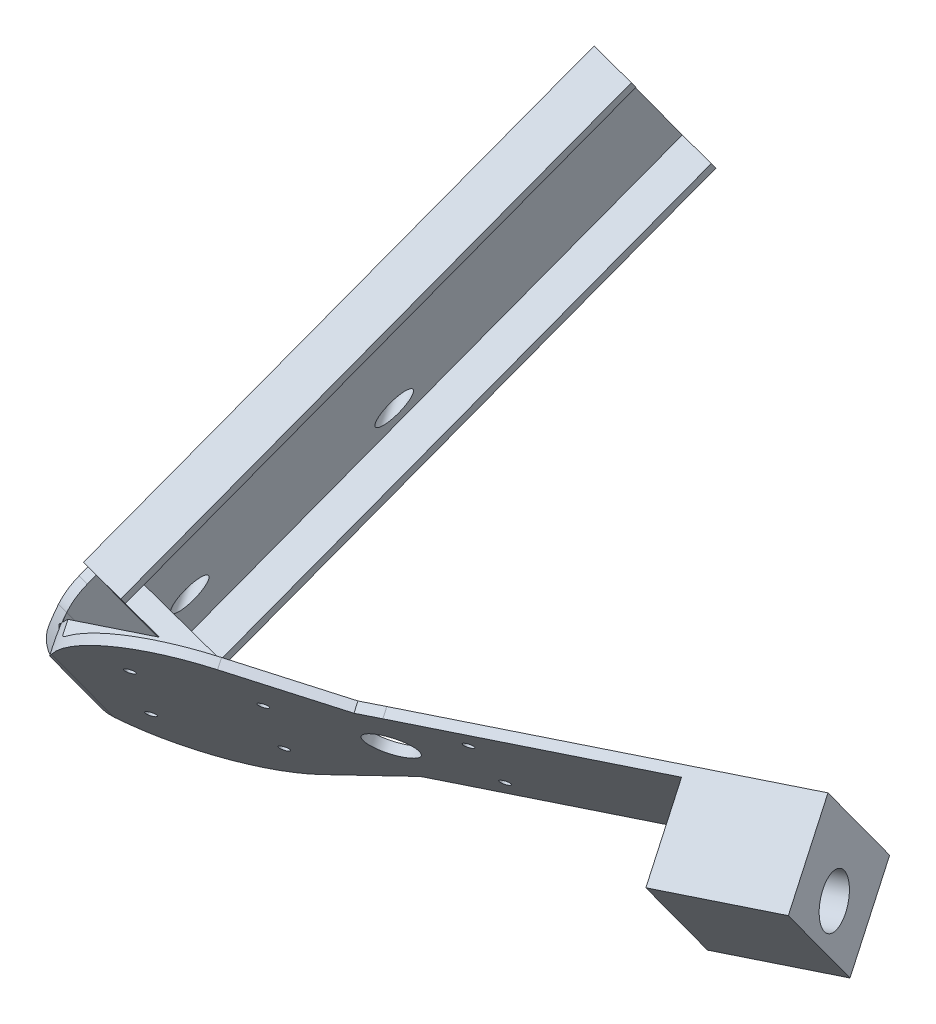
SolidWorks part; units mm, degrees
ref_plane "Front Plane" through (0, 0, 0) normal (0, 0, 1) x (1, 0, 0)
ref_plane "Top Plane" through (0, 0, 0) normal (0, 1, 0) x (1, 0, 0)
ref_plane "Right Plane" through (0, 0, 0) normal (1, 0, 0) x (0, 0, -1)
sketch "Sketch2" plane through (20.5367, -40.368, 48.4426) normal (-0.3097, 0.6087, -0.7305) x (-0.9432, -0.0997, 0.3168)
  line L14 (99.8599, 39.0261) -> (80.3467, 30.0123)
  line L15 (80.3467, 30.0123) -> (75.4661, 30.0566)
  line L16 (75.4661, 30.0566) -> (53.4661, 30.0566)
  line L17 (53.4661, 30.0566) -> (53.4661, 3.0572)
  line L18 (53.4661, 3.0572) -> (75.3438, 3.0572)
  line L19 (75.3438, 3.0572) -> (79.5451, 3.0191)
  line L20 (79.5451, 3.0191) -> (99.8599, -6.365)
  arc A2 (99.8599, -6.365) -> (99.8599, 39.0261) centre (110.3438, 16.3306) ccw
  circle A7 centre (118.4981, 28.9205) radius 1
  circle A8 centre (122.9337, 8.1762) radius 1
  circle A9 centre (102.1894, 3.7406) radius 1
  circle A10 centre (97.7538, 24.4849) radius 1
extrude "Boss-Extrude1" add sketch "Sketch2" along normal blind 2
ref_plane "Plane2" through (-127.6606, -13.4871, 42.8812) normal (-0.9432, -0.0997, 0.3168) x (0.3173, 0.0115, 0.9483)
sketch "Sketch5" plane through (19.9173, -39.1506, 46.9817) normal (-0.3097, 0.6087, -0.7305) x (-0.9432, -0.0997, 0.3168)
  line L0 (135.3438, 30.0566) -> (135.3438, 0)
  line L1 (135.3438, -27.1851) -> (135.3438, 27.1851) construction
  line L2 (135.3438, 30.0566) -> (53.4661, 30.0566) construction
  line L3 (53.4661, 30.0566) -> (53.4661, 3.0572) construction
  line L4 (75.4661, 30.0566) -> (53.4661, 30.0566) construction
  line L5 (53.4661, 30.0566) -> (53.4661, 3.0572) construction
  line L6 (53.4661, 3.0572) -> (135.3438, 3.0572) construction
ref_plane "Plane3" through (-82.6453, 18.546, -7.7268) normal (-0.9717, 0.2181, -0.0908) x (-0.1201, -0.7871, -0.605)
sketch "Sketch7" plane through (-82.6453, 18.546, -7.7268) normal (-0.9717, 0.2181, -0.0908) x (-0.1201, -0.7871, -0.605)
  line L0 (-32.8306, 125.1046) -> (-16.3306, 131.4663) construction
  line L5 (-41.3306, 110.8725) -> (8.6694, 110.8725) construction
  line L6 (-16.3306, 110.8725) -> (-16.3306, 131.4663) construction
  line L7 (-32.8306, 125.1046) -> (0.1694, 125.1046)
  line L8 (-32.8306, 125.1046) -> (-32.8306, 0.9406)
  line L9 (-32.8306, 0.9406) -> (0.1694, 0.9406)
  line L10 (0.1694, 125.1046) -> (0.1694, 0.9406)
  line L11 (-16.3306, 131.4663) -> (0.1694, 125.1046) construction
  ellipse E0 centre (-16.3306, 112.6046) end of major axis (-41.3306, 112.6046) minor radius 12.5 (6.365, 107.3626) -> (-39.0261, 107.3626) ccw construction
  dimension "D1" = 33
  dimension "D2" = 124.164
extrude "Boss-Extrude4" add sketch "Sketch7" against normal blind 2
sketch "Sketch8" plane through (20.5367, -40.368, 48.4426) normal (0.3097, -0.6087, 0.7305) x (0.9508, 0.1982, -0.2379)
  circle A0 centre (-76.6465, 26.2189) radius 4.75
  dimension "D1" = 9.5
extrude "Cut-Extrude1" cut sketch "Sketch8" against normal up to next
sketch "Sketch10" plane through (20.5367, -40.368, 48.4426) normal (0.3097, -0.6087, 0.7305) x (0.9508, 0.1982, -0.2379)
  circle A0 centre (-123.8351, 33.3692) radius 33.6087
extrude "Cut-Extrude2" cut sketch "Sketch10" along normal blind 2
fillet "Fillet5" radius 3 1 edges at (-103.6043, -39.5536, 99.0114)
sketch "Sketch11" plane through (-80.7019, 18.1099, -7.5451) normal (0.9717, -0.2181, 0.0908) x (0.0886, -0.0199, -0.9959)
  line L4 (-118.8575, -49.576) -> (-20.6925, 25.5059) construction
  line L5 (-108.7694, -41.86) -> (-118.8575, -49.576)
  line L6 (-0.6442, -0.706) -> (-98.8092, -75.7879) construction
  line L7 (-90.6097, -69.5165) -> (-98.5614, -75.5983)
  line L8 (-113.3959, -56.7166) -> (-122.236, -62.9515)
  line L9 (-122.236, -62.9515) -> (-127.4435, -56.143)
  line L10 (-127.4435, -56.143) -> (-118.8575, -49.576)
  line L11 (-98.5614, -75.5983) -> (-107.3952, -82.3549)
  line L12 (-107.3952, -82.3549) -> (-112.8567, -75.2142)
  line L13 (-112.8567, -75.2142) -> (-104.2708, -68.6472)
  arc A0 (-111.9091, -46.3062) -> (-108.7694, -41.86) centre (-102.9159, -49.3252) cw
  arc A1 (-93.8342, -69.938) -> (-90.6097, -69.5165) centre (-95.1843, -47.0658) ccw
  ellipse E0 centre (-70.9526, -33.7087) end of major axis (-110.6677, -64.0849) minor radius 25 (-104.2708, -68.6472) -> (-93.8342, -69.938) ccw construction
  ellipse E1 centre (-70.9526, -33.7087) end of major axis (-110.6677, -64.0849) minor radius 25 (-111.9091, -46.3062) -> (-113.3959, -56.7166) ccw construction
  ellipse E2 centre (-70.9526, -33.7087) end of major axis (-110.6677, -64.0849) minor radius 25 (-104.2708, -68.6472) -> (-93.8342, -69.938) ccw
  ellipse E3 centre (-70.9526, -33.7087) end of major axis (-110.6677, -64.0849) minor radius 25 (-111.9091, -46.3062) -> (-113.3959, -56.7166) ccw
extrude "Cut-Extrude3" cut sketch "Sketch11" against normal blind 2
fillet "Fillet6" radius 3 1 edges at (-106.1336, -40.7743, 101.1199)
fillet "Fillet7" radius 3 1 edges at (-105.1619, -40.9923, 101.2107)
sketch "Sketch12" plane through (19.9173, -39.1506, 46.9817) normal (-0.3097, 0.6087, -0.7305) x (-0.9508, -0.1982, 0.2379)
  line L0 (122.6698, 48.7105) -> (108.6205, 46.9221)
  line L1 (124.388, 48.9292) -> (69.3888, 41.9282) construction
  line L2 (108.6205, 46.9221) -> (112.7875, 14.1862)
  line L3 (73.5558, 9.1923) -> (129.7344, 16.3434) construction
  line L4 (112.7875, 14.1862) -> (126.8363, 15.9745)
  line L5 (127.0079, 14.6264) -> (122.4977, 50.0585) construction
  line L7 (108.6205, 46.9221) -> (122.6698, 48.7105)
  line L8 (122.6698, 48.7105) -> (126.5456, 49.2038)
  line L9 (126.5456, 49.2038) -> (130.7126, 16.468)
  line L10 (130.7126, 16.468) -> (126.8363, 15.9745)
  circle A0 centre (120.9172, 23.6341) radius 1 construction
  circle A1 centre (113.8977, 43.6522) radius 1 construction
  circle A2 centre (120.9172, 23.6341) radius 1
  circle A3 centre (113.8977, 43.6522) radius 1
  circle M10 centre (113.8977, 43.6522) radius 1
  circle M11 centre (120.9172, 23.6341) radius 1
  line M14 (127.0079, 14.6264) -> (122.4977, 50.0585)
extrude "Boss-Extrude5" add sketch "Sketch12" along normal blind 3 contours L2 L4 L0 M14 M10 M11 | L10 L9 L8 L0 M14 region at (-100.5459, -39.2305, 97.9841) region at (-92.0281, -38.354, 95.1034)
sketch "Sketch13" plane through (18.9883, -37.3245, 44.7903) normal (-0.3097, 0.6087, -0.7305) x (-0.9508, -0.1982, 0.2379)
  circle A0 centre (113.8977, 43.6522) radius 2
  circle A1 centre (120.9172, 23.6341) radius 2
  dimension "D1" = 4
extrude "Cut-Extrude4" cut sketch "Sketch13" against normal blind 3
sketch "Sketch14" plane through (20.5367, -40.368, 48.4426) normal (0.3097, -0.6087, 0.7305) x (0.9508, 0.1982, -0.2379)
  line L0 (-126.5456, 49.2038) -> (-126.9975, 45.6535)
  line L1 (-126.5456, 49.2038) -> (-123.9462, 48.8729)
  line L2 (-130.2607, 20.0182) -> (-130.7126, 16.468)
  line L3 (-130.7126, 16.468) -> (-128.1132, 16.1371)
  arc A0 (-123.9462, 48.8729) -> (-126.9975, 45.6535) centre (-107.3984, 30.1334) ccw construction
  arc A1 (-123.9462, 48.8729) -> (-126.9975, 45.6535) centre (-107.3984, 30.1334) ccw
  arc A2 (-131.6151, 23.9243) -> (-129.9101, 19.2604) centre (-107.3984, 30.1334) ccw construction
  arc A3 (-130.2607, 20.0182) -> (-129.9101, 19.2604) centre (-107.3984, 30.1334) ccw
  arc A4 (-129.9101, 19.2604) -> (-99.8643, 6.2956) centre (-107.3984, 30.1334) ccw construction
  arc A5 (-129.9101, 19.2604) -> (-128.1132, 16.1371) centre (-107.3984, 30.1334) ccw
extrude "Cut-Extrude5" cut sketch "Sketch14" against normal up to surface (5 mm away) up to face at (-89.3106, -24.8328, 101.1118)
sketch "Sketch17" plane through (-80.7019, 18.1099, -7.5451) normal (0.9717, -0.2181, 0.0908) x (0.0886, -0.0199, -0.9959)
  line L0 (-107.2713, -40.7142) -> (-87.223, -66.9262) construction
  line L1 (-107.2713, -40.7142) -> (-87.223, -66.9262)
  line L2 (-107.2713, -40.7142) -> (-104.0941, -38.2841)
  line L3 (-108.7694, -41.86) -> (-20.6925, 25.5059) construction
  line L4 (-104.0941, -38.2841) -> (-84.0458, -64.4961)
  line L5 (-0.6442, -0.706) -> (-90.6097, -69.5165) construction
  line L6 (-84.0458, -64.4961) -> (-87.223, -66.9262)
  dimension "D1" = 4
extrude "Boss-Extrude7" add sketch "Sketch17" along normal up to vertex (15.2648 mm away) separate body up to point (-88.255, -48.7857, 80.704)
sketch "Sketch18" plane through (3.9419, 25.8413, 19.8629) normal (0.1201, 0.7871, 0.605) x (0.9928, -0.0952, -0.0732)
  line L0 (-88.058, -89.8018) -> (-75.4041, -92.451)
  line L1 (-74.815, -92.2576) -> (-56.2754, -86.1709) construction
  line L2 (-75.4041, -92.451) -> (-87.9418, -96.5673)
  line L3 (-87.9418, -96.5673) -> (-88.8776, -93.7169)
  line L4 (-88.8776, -93.7169) -> (-88.058, -89.8018)
  line L5 (-88.058, -89.8018) -> (-102.9988, -86.6738) construction
extrude "Boss-Extrude8" add sketch "Sketch18" against normal up to surface (33 mm away) up to face at (-95.2645, -45.9675, 78.4285)
sketch "Sketch16" plane through (19.9173, -39.1506, 46.9817) normal (-0.3097, 0.6087, -0.7305) x (-0.9508, -0.1982, 0.2379)
  circle A0 centre (120.9172, 23.6341) radius 2 construction
  circle A1 centre (113.8977, 43.6522) radius 2 construction
  circle A2 centre (120.9172, 23.6341) radius 2
  circle A3 centre (113.8977, 43.6522) radius 2
extrude "Cut-Extrude6" cut sketch "Sketch16" along normal through all
sketch "Sketch20" plane through (19.9173, -39.1506, 46.9817) normal (-0.3097, 0.6087, -0.7305) x (-0.9508, -0.1982, 0.2379)
  circle A0 centre (100.8991, 16.6145) radius 2
  dimension "D1" = 4
extrude "Cut-Extrude7" cut sketch "Sketch20" along normal through all
sketch "Sketch21" plane through (3.9419, 25.8413, 19.8629) normal (0.1201, 0.7871, 0.605) x (0.9928, -0.0952, -0.0732)
  line L0 (-83.4403, 16.5079) -> (-105.776, -90.1791)
  line L1 (-106.1625, -92.0251) -> (-83.4403, 16.5079) construction
  line L2 (-105.776, -90.1791) -> (-96.967, -92.0234)
  line L3 (-96.967, -92.0234) -> (-74.6312, 14.6636)
  line L4 (-74.6312, 14.6636) -> (-83.4403, 16.5079)
  line L5 (-88.8776, -93.7169) -> (-103.8185, -90.589) construction
  dimension "D1" = 9
extrude "Boss-Extrude9" add sketch "Sketch21" along normal blind 2
sketch "Sketch22" plane through (-0.0203, -0.1334, -0.1025) normal (-0.1201, -0.7871, -0.605) x (0.9928, -0.0952, -0.0732)
  line L3 (-105.776, 90.1791) -> (-96.967, 92.0234)
  line L11 (-88.8776, 93.7169) -> (-103.8185, 90.589) construction
  line L12 (-74.6312, -14.6636) -> (-96.967, 92.0234)
  line L13 (-96.1473, 88.1082) -> (-74.6312, -14.6636) construction
  line L14 (-105.776, 90.1791) -> (-83.4403, -16.5079)
  line L15 (-83.4403, -16.5079) -> (-74.6312, -14.6636)
extrude "Boss-Extrude10" add sketch "Sketch22" along normal blind 2 separate body
sketch "Sketch23" plane through (3.6088, 23.6579, 18.1846) normal (0.1201, 0.7871, 0.605) x (0.9928, -0.0952, -0.0732)
  line L0 (-30.736, -77.7861) -> (-30.1122, -79.6863)
  line L1 (-30.1122, -79.6863) -> (-3.205, -70.8524)
  line L2 (19.5975, -63.3662) -> (18.9737, -61.4659)
  line L3 (18.9737, -61.4659) -> (-30.736, -77.7861)
  line L4 (-3.205, -70.8524) -> (2.4097, -87.9543)
  line L5 (2.4097, -87.9543) -> (25.2123, -80.4681)
  line L6 (25.2123, -80.4681) -> (19.5975, -63.3662)
  dimension "D1" = 20
  dimension "D2" = 24
extrude "Boss-Extrude11" add sketch "Sketch23" against normal up to surface (26.9994 mm away) up to face at (-40.1548, -43.771, 69.9673)
sketch "Sketch24" plane through (-1.0809, -0.1142, 0.3631) normal (0.9432, 0.0997, -0.3168) x (-0.3151, -0.0333, -0.9485)
  line L0 (-75.4976, -41.0328) -> (-60.0948, -28.2754) construction
  line L1 (-66.8865, -51.4295) -> (-84.1087, -30.6362) construction
  line L2 (-51.4837, -38.672) -> (-68.7059, -17.8787) construction
sketch "Sketch25" plane through (-1.0809, -0.1142, 0.3631) normal (0.9432, 0.0997, -0.3168) x (-0.3151, -0.0333, -0.9485)
  circle A0 centre (-69.6498, -36.3354) radius 5
  point P2 (0, 0)
  point P3 (0, 0)
extrude "Cut-Extrude8" cut sketch "Sketch25" against normal blind 35
sketch "Sketch26" plane through (19.9173, -39.1506, 46.9817) normal (-0.3097, 0.6087, -0.7305) x (-0.9508, -0.1982, 0.2379)
  line L0 (58.8451, 37.7897) -> (62.2544, 11.0064) construction
  line L1 (71.0667, 39.3454) -> (21.1493, 32.9913) construction
  line L2 (24.5586, 6.208) -> (74.3546, 12.5467) construction
  line L3 (49.9172, 36.6533) -> (53.3265, 9.8699) construction
  line L4 (61.56, 16.4621) -> (49.9172, 36.6533) construction
  line L5 (59.5396, 32.334) -> (53.3265, 9.8699) construction
  line L6 (0.7507, 3.1774) -> (-2.6586, 29.9607) construction
  circle A0 centre (59.5396, 32.334) radius 1
  circle A1 centre (61.56, 16.4621) radius 1
  point P10 (59.4922, 32.328)
  dimension "D2" = 2
  dimension "D1" = 16
  dimension "D3" = 9
  dimension "D4" = 62
extrude "Cut-Extrude10" cut sketch "Sketch26" against normal blind 35
